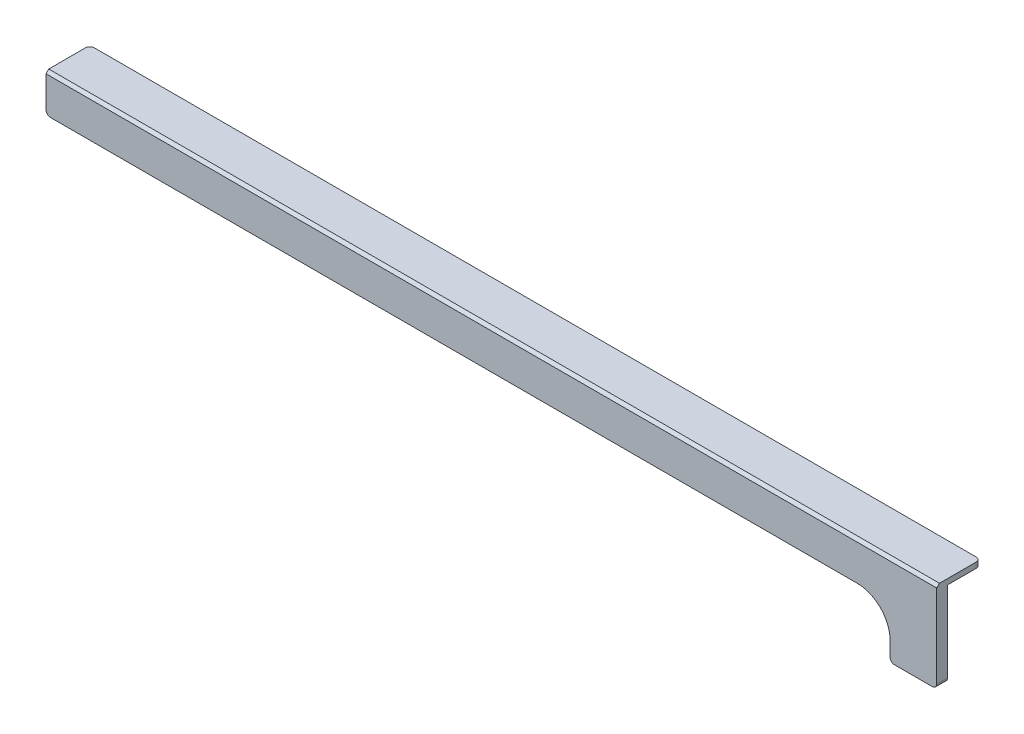
SolidWorks part; units mm, degrees
material "Brass"
ref_plane "Front Plane" through (0, 0, 0) normal (0, 0, 1) x (1, 0, 0)
ref_plane "Top Plane" through (0, 0, 0) normal (0, 1, 0) x (1, 0, 0)
ref_plane "Right Plane" through (0, 0, 0) normal (1, 0, 0) x (0, 0, -1)
ref_plane "Plane1" through (0, 0, 2.6038) normal (0, 0, -1) x (-1, 0, 0)
ref_plane "Plane2" through (0, 63.6237, 0) normal (0, -1, 0) x (-1, 0, 0)
sketch "Sketch1" plane through (0, 63.6237, 0) normal (0, -1, 0) x (-1, 0, 0)
  line L0 (-230.4632, 0) -> (230.4632, 0) construction
  point P4 (0, 0)
sketch "Sketch2" plane through (0, 0, 14.1038) normal (0, 0, 1) x (1, 0, 0)
  line L0 (125.9748, 57.6246) -> (-157.6246, 57.6246) construction
  line L1 (165.5748, 59.6246) -> (-159.2246, 59.6246) construction
  line L4 (163.9748, 38.6744) -> (129.1748, 38.6744) construction
  line L5 (-159.2246, 59.6246) -> (-159.2246, 73.6246)
  line L6 (-159.2246, 73.6246) -> (165.5748, 73.6246)
  line L7 (165.5748, 73.6246) -> (165.5748, 59.6246)
  line L9 (165.5748, 59.6246) -> (165.5748, 40.6744)
  line L10 (165.5748, 40.6744) -> (148.5758, 40.6744)
  line L11 (148.5758, 40.6744) -> (148.5758, 59.6246)
  line L12 (148.5758, 59.6246) -> (-159.2246, 59.6246)
  line L14 (165.5748, -56.0248) -> (165.5748, 37.0744) construction
  line L15 (148.5758, 35.5747) -> (148.5758, 21.5754) construction
  line L18 (-159.2246, 56.0246) -> (-159.2246, 39.6997) construction
  dimension "D1" = 2
  dimension "D3" = 2
extrude "Boss-Extrude1" add sketch "Sketch2" against normal blind 4
sketch "Sketch3" plane through (0, 73.6246, 0) normal (0, 1, 0) x (1, 0, 0)
  line L0 (165.5748, -10.1038) -> (-159.2246, -10.1038) construction
  line L1 (165.5748, -10.1038) -> (-159.2246, -10.1038)
  line L2 (-159.2246, -10.1038) -> (-159.2246, 1.8962)
  line L3 (-159.2246, 1.8962) -> (165.5748, 1.8962)
  line L4 (165.5748, 1.8962) -> (165.5748, -10.1038)
  line L6 (177.5748, -14.1038) -> (131.5748, -14.1038) construction
  dimension "D1" = 16
extrude "Boss-Extrude2" add sketch "Sketch3" against normal blind 2
fillet "Fillet1" radius 1 1 edges at (3.1751, 73.6246, 14.1038) profile chamfer
fillet "Fillet2" radius 1.6 5 edges at (-159.2246, 72.6246, -1.8962) (165.5748, 72.6246, -1.8962) (165.5748, 40.6744, 12.1038) (148.5758, 40.6744, 12.1038) (-159.2246, 59.6246, 12.1038)
fillet "Fillet3" radius 12 1 edges at (148.5758, 59.6246, 12.1038)
hole_wizard "Tap Drill for M3x0.5 Tap1" positions "Sketch4" profile "Sketch5" hole size "M3x0.5" standard "ANSI Metric"
sketch "Sketch4" plane through (0, 0, 5.0798) normal (0, 0, -1) x (-1, 0, 0)
  point P0 (-106.6149, 66.6237)
  point P3 (-37.655, 66.6237)
  point P6 (31.3048, 66.6237)
  point P9 (100.2647, 66.6237)
  point P12 (100.2647, -66.6248)
  point P15 (31.3048, -66.6248)
  point P18 (-37.655, -66.6248)
  point P21 (-106.6149, -66.6248)
sketch "Sketch5" plane through (106.6149, 66.6237, 5.0798) normal (1, 0, 0) x (0, 1, 0)
  line L0 (0, 0) -> (0, 7.7511)
  line L1 (0, 7.7511) -> (1.25, 7)
  line L2 (1.25, 7) -> (1.25, 0.025)
  line L3 (1.25, 0.025) -> (1.275, 0)
  line L4 (1.275, 0) -> (0, 0)
  line L5 (-1.25, 0.025) -> (-1.275, 0) construction
  line L6 (0, 7.7511) -> (-1.25, 7) construction
  line L7 (0, -6.35) -> (0, 107.95) construction
  dimension "Hole Dia." = 2.5
  dimension "Hole Depth" = 7
  dimension "Near C'Sink Dia." = 2.55
  dimension "Near C'Sink Angle" = 90
  dimension "Drill Angle" = 118
hole_wizard "CBORE for M2.5 Hex Socket Head Cap Screw1" positions "Sketch6" profile "Sketch7" counterbore size "M2.5" standard "DIN"
sketch "Sketch6" plane through (0, 0, -6) normal (0, 0, 1) x (1, 0, 0)
  point P0 (-168.7241, -67.1243)
  point P3 (175.0743, -67.1243)
  point P6 (175.0743, 67.1241)
  point P9 (72.135, 67.1241)
  point P12 (-65.7848, 67.1241)
  point P15 (-168.7241, 67.1241)
sketch "Sketch7" plane through (-168.7241, -67.1243, -6) normal (1, 0, 0) x (0, 1, 0)
  line L0 (0, 0) -> (0, 18.8712)
  line L1 (0, 18.8712) -> (1.45, 18)
  line L2 (1.45, 18) -> (1.45, 5.9)
  line L3 (1.45, 5.9) -> (2.75, 5.9)
  line L4 (2.75, 5.9) -> (2.75, 0.025)
  line L5 (2.75, 0.025) -> (2.775, 0)
  line L6 (2.775, 0) -> (0, 0)
  line L7 (-2.75, 0.025) -> (-2.775, 0) construction
  line L8 (0, 18.8712) -> (-1.45, 18) construction
  line L9 (0, -6.35) -> (0, 107.95) construction
  dimension "Hole Dia." = 2.9
  dimension "Hole Depth" = 18
  dimension "C'Bore Dia." = 5.5
  dimension "C'Bore Depth" = 5.9
  dimension "Near C'Sink Dia." = 5.55
  dimension "Near C'Sink Angle" = 90
  dimension "Drill Angle" = 118
